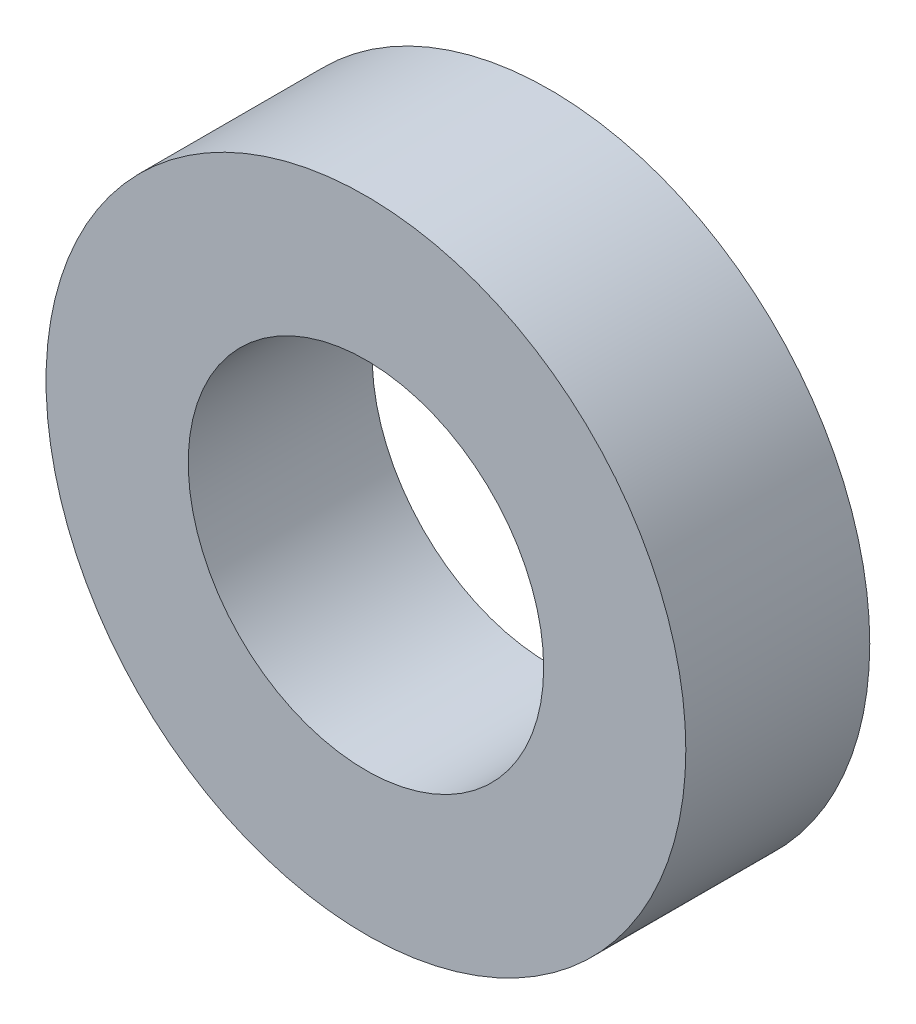
SolidWorks part; units mm, degrees
material "ABS"
ref_plane "Front Plane" through (0, 0, 0) normal (0, 0, 1) x (1, 0, 0)
ref_plane "Top Plane" through (0, 0, 0) normal (0, 1, 0) x (1, 0, 0)
ref_plane "Right Plane" through (0, 0, 0) normal (1, 0, 0) x (0, 0, -1)
sketch "Sketch1" plane through (0, 0, 0) normal (0, 0, 1) x (1, 0, 0)
  circle A0 centre (0, 0) radius 2.5
  circle A1 centre (0, 0) radius 4.5
  dimension "D1" = 5
  dimension "D2" = 9
extrude "Boss-Extrude1" add sketch "Sketch1" along normal mid plane 2.5875
